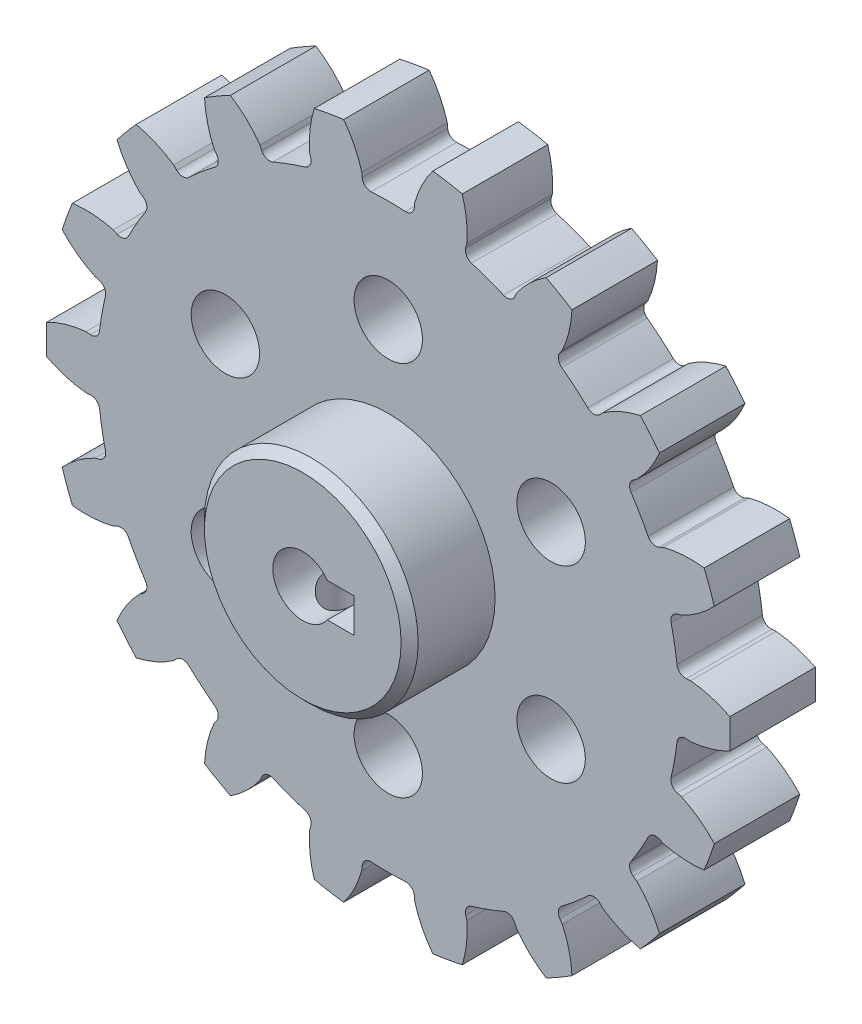
SolidWorks part; units mm, degrees
ref_plane "Plan de face" through (0, 0, 0) normal (0, 0, 1) x (1, 0, 0)
ref_plane "Plan de dessus" through (0, 0, 0) normal (0, 1, 0) x (1, 0, 0)
ref_plane "Plan de droite" through (0, 0, 0) normal (1, 0, 0) x (0, 0, -1)
sketch "Esquisse1" plane through (0, 0, 0) normal (0, 0, 1) x (1, 0, 0)
  line L0 (0, 0) -> (49.1646, 0) construction
  line L1 (0, 0) -> (33.4835, 5.904) construction
  line L2 (0, 0) -> (40.5362, 3.5465) construction
  line L3 (0, 0) -> (40.5296, 1.7696) construction
  line L4 (33.8706, -2.9633) -> (35.3649, -3.094)
  line L5 (0, 0) -> (33.4835, 5.904)
  line L6 (33.8706, 2.9633) -> (35.3649, 3.094)
  line L7 (0, 0) -> (33.4835, -5.904)
  circle A0 centre (0, 0) radius 40 construction
  circle A1 centre (0, 0) radius 35.5 construction
  circle A2 centre (0, 0) radius 34 construction
  arc A3 (33.4835, 5.904) -> (33.8706, 2.9633) centre (0, 0) cw
  arc A4 (39.9546, -1.7445) -> (39.9546, 1.7445) centre (0, 0) ccw
  arc A5 (35.3649, 3.094) -> (39.9546, 1.7445) centre (34.1869, -9.3916) cw
  arc A6 (35.3649, -3.094) -> (39.9546, -1.7445) centre (34.1869, 9.3916) ccw
  arc A7 (33.4835, -5.904) -> (33.8706, -2.9633) centre (0, 0) ccw
  dimension "D1" = 80
  dimension "D2" = 71
  dimension "D3" = 6
  dimension "D4" = 10
  dimension "D5" = 5
  dimension "D6" = 2.5
extrude "Boss.-Extru.1" add sketch "Esquisse1" along normal blind 10 contours L7 A7 L4 A6 A4 A5 L6 A3 L5
fillet "Congé1" radius 1 2 edges at (33.8706, -2.9633, 5) (33.8706, 2.9633, 5)
pattern_circular "Répétition circulaire2" count 18 over 360 about axis through (0, 0, 10) along (0, 0, -1) of "Congé1", "Boss.-Extru.1" reverse direction yes
sketch "Esquisse3" plane through (0, 0, 10) normal (0, 0, 1) x (1, 0, 0)
  circle A0 centre (0, 0) radius 12.5
  dimension "D1" = 25
extrude "Boss.-Extru.2" add sketch "Esquisse3" along normal blind 10
sketch "Esquisse5" plane through (0, 0, 20) normal (0, 0, 1) x (1, 0, 0)
  circle A0 centre (0, 0) radius 3.5
  dimension "D1" = 7
sketch "Esquisse7" plane through (0, 0, 20) normal (0, 0, 1) x (1, 0, 0)
  line L1 (0, 2) -> (6, 2)
  line L2 (0, 2) -> (0, -2)
  line L3 (0, -2) -> (6, -2)
  line L4 (6, 2) -> (6, -2)
  dimension "D1" = 2
  dimension "D2" = 2
  dimension "D3" = 6
extrude "Enlèv. mat.-Extru.2" cut sketch "Esquisse7" against normal up to surface (10 mm away) contours L1 L4 L3 L2 up to face at (-12.5, 0, 10)
extrude "Enlèv. mat.-Extru.3" cut sketch "Esquisse5" against normal up to surface (20 mm away) up to face at (0, 0, 0)
sketch "Esquisse8" plane through (0, 0, 0) normal (0, 1, 0) x (1, 0, 0)
  line L0 (-12.5, -20) -> (12.5, -20) construction
  circle A0 centre (0, -15) radius 2.5
  dimension "D1" = 5
  dimension "D2" = 5
extrude "Enlèv. mat.-Extru.4" cut sketch "Esquisse8" against normal up to surface (12.5 mm away) contours A0 up to face at (12.5, 0, 20)
chamfer "Chanfrein1" distance 1 angle 45 1 edges at (12.5, 0, 20)
sketch "Esquisse9" plane through (0, 0, 10) normal (0, 0, 1) x (1, 0, 0)
  circle A0 centre (0, 22) radius 4
  dimension "D1" = 8
  dimension "D2" = 22
extrude "Enlèv. mat.-Extru.5" cut sketch "Esquisse9" against normal up to surface (10 mm away) up to face at (-3.5, 0, 0)
pattern_circular "Répétition circulaire3" count 6 over 360 about axis through (0, 0, 20) along (0, 0, -1) of "Enlèv. mat.-Extru.5"
